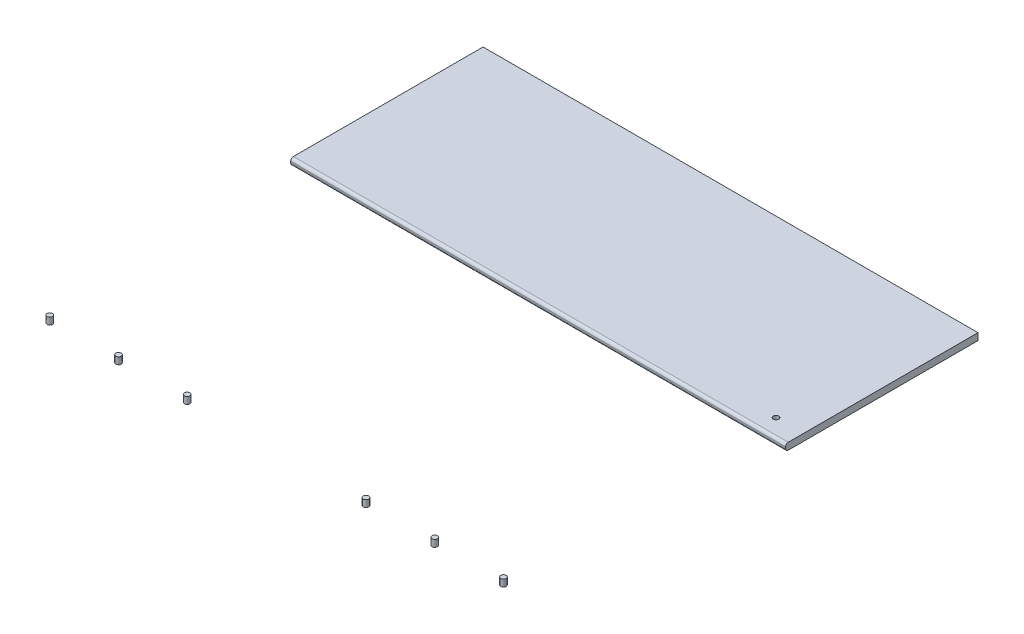
SolidWorks part; units mm, degrees
material "6061 Alloy"
ref_plane "Front Plane" through (0, 0, 0) normal (0, 0, 1) x (1, 0, 0)
ref_plane "Top Plane" through (0, 0, 0) normal (0, 1, 0) x (1, 0, 0)
ref_plane "Right Plane" through (0, 0, 0) normal (1, 0, 0) x (0, 0, -1)
sketch "Sketch1" plane through (0, 0, 0) normal (0, 1, 0) x (1, 0, 0)
  line L1 (-228.6, 88.9) -> (228.6, 88.9)
  line L2 (-228.6, 88.9) -> (-228.6, -88.9)
  line L3 (-228.6, -88.9) -> (228.6, -88.9)
  line L4 (228.6, 88.9) -> (228.6, -88.9)
  line L5 (-228.6, 88.9) -> (228.6, -88.9) construction
  line L6 (-228.6, -88.9) -> (228.6, 88.9) construction
  circle A10 centre (204.7875, -325.6513) radius 2.5019 construction
  circle A11 centre (141.2875, -325.6513) radius 2.5019 construction
  circle A12 centre (77.7875, -325.6513) radius 2.5019 construction
  circle A13 centre (-87.3125, -325.6513) radius 2.5019 construction
  circle A14 centre (-150.8125, -325.6513) radius 2.5019 construction
  circle A15 centre (-214.3125, -325.6513) radius 2.5019 construction
  circle A16 centre (204.7875, -325.6513) radius 2.5019
  circle A17 centre (141.2875, -325.6513) radius 2.5019
  circle A18 centre (77.7875, -325.6513) radius 2.5019
  circle A19 centre (-87.3125, -325.6513) radius 2.5019
  circle A20 centre (-150.8125, -325.6513) radius 2.5019
  circle A21 centre (-214.3125, -325.6513) radius 2.5019
  point P0 (0, 0)
  dimension "D1" = 177.8
  dimension "D2" = 457.2
extrude "Boss-Extrude1" add sketch "Sketch1" along normal blind 6.35
sketch "Sketch2" plane through (-228.6, 0, 0) normal (-1, 0, 0) x (0, 0, 1)
  line L0 (-88.9, 6.35) -> (88.9, 6.35) construction
  line L1 (88.9, 6.35) -> (88.9, 0) construction
  circle A0 centre (85.725, 3.175) radius 1.5875
  dimension "D1" = 3.175
  dimension "D2" = 3.175
  dimension "D3" = 3.175
extrude "Cut-Extrude1" [suppressed] cut sketch "Sketch2" against normal through all
fillet "Fillet1" radius 2.54 2 edges at (0, 0, 88.9) (0, 6.35, 88.9)
sketch "Sketch3" plane through (228.6, 0, 0) normal (1, 0, 0) x (0, 0, -1)
  line L0 (88.9, 6.35) -> (88.9, 0) construction
  line L1 (-48.26, 4.572) -> (-33.02, 4.572)
  line L2 (-48.26, 4.572) -> (-48.26, 1.27)
  line L3 (-48.26, 1.27) -> (-33.02, 1.27)
  line L4 (-33.02, 4.572) -> (-33.02, 1.27)
  line L5 (-48.26, 4.572) -> (-33.02, 1.27) construction
  line L6 (-48.26, 1.27) -> (-33.02, 4.572) construction
  line L7 (-86.36, 0) -> (88.9, 0) construction
  point P0 (-40.64, 2.921)
  dimension "D1" = 15.24
  dimension "D2" = 129.54
  dimension "D3" = 3.302
  dimension "D4" = 1.27
sketch "Sketch4" plane through (0, 0, 0) normal (0, -1, 0) x (1, 0, 0)
  line L0 (228.6, 86.36) -> (228.6, -88.9) construction
  line L2 (-228.6, 88.9) -> (228.6, 88.9) construction
  circle A1 centre (203.2, 72.3392) radius 2.54
  dimension "D2" = 5.08
  dimension "D1" = 16.5608
  dimension "D3" = 25.4
extrude "Cut-Extrude3" cut sketch "Sketch4" against normal through all
sketch "Sketch5" plane through (0, 0, 0) normal (0, -1, 0) x (1, 0, 0)
  line L0 (-228.6, 88.9) -> (228.6, 88.9) construction
  line L1 (-222.25, 61.1632) -> (-69.85, 61.1632)
  line L2 (-222.25, 61.1632) -> (-222.25, 88.9)
  line L3 (-222.25, 88.9) -> (-69.85, 88.9)
  line L4 (-69.85, 61.1632) -> (-69.85, 88.9)
  line L5 (-228.6, -88.9) -> (-228.6, 86.36) construction
  dimension "D1" = 6.35
  dimension "D2" = 152.4
  dimension "D3" = 27.7368
ref_axis "Axis1" through (0, 0, -88.9) along (0, 0.0143, 0.9999)
ref_plane "Plane1" through (0, 0, 0) normal (1, 0, 0) x (0, 0, -1)
